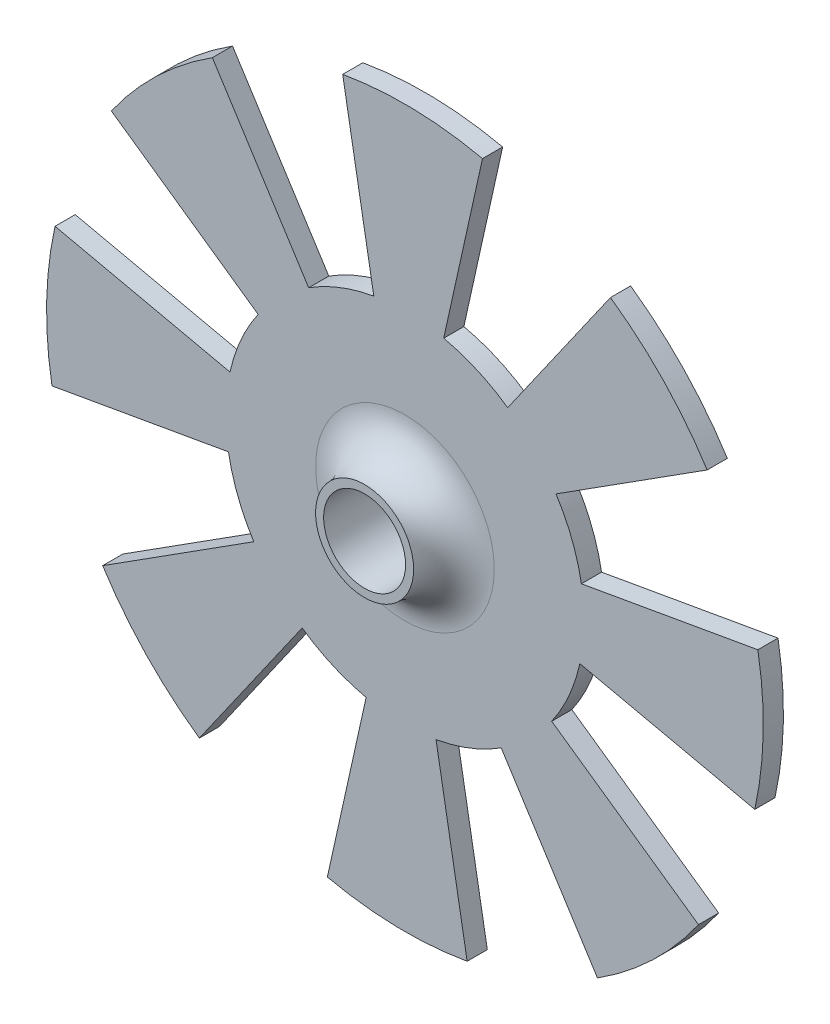
SolidWorks part; units mm, degrees
ref_plane "Front Plane" through (0, 0, 0) normal (0, 0, 1) x (1, 0, 0)
ref_plane "Top Plane" through (0, 0, 0) normal (0, 1, 0) x (1, 0, 0)
ref_plane "Right Plane" through (0, 0, 0) normal (1, 0, 0) x (0, 0, -1)
sketch "Sketch1" plane through (0, 0, 0) normal (0, 0, 1) x (1, 0, 0)
  circle A0 centre (0, 0) radius 8.89
  circle A1 centre (0, 0) radius 1.016
  dimension "D1" = 17.78
  dimension "D2" = 2.032
extrude "Boss-Extrude1" add sketch "Sketch1" against normal blind 0.5
sketch "Sketch2" plane through (0, 0, 0) normal (0, 0, 1) x (1, 0, 0)
  line L0 (-0.7719, 4.3775) -> (-1.5437, 8.7549)
  line L1 (2.5495, 3.6411) -> (5.0991, 7.2823)
  line L2 (4.3775, 0.7719) -> (8.7549, 1.5437)
  line L3 (3.6411, -2.5495) -> (7.2823, -5.0991)
  line L4 (0.7719, -4.3775) -> (1.5437, -8.7549)
  line L5 (-2.5495, -3.6411) -> (-5.0991, -7.2823)
  line L6 (-4.3775, -0.7719) -> (-8.7549, -1.5437)
  line L7 (-3.6411, 2.5495) -> (-7.2823, 5.0991)
  line L8 (0.9621, 4.3396) -> (1.9241, 8.6793)
  line L9 (2.5495, 3.6411) -> (5.0991, 7.2823)
  line L10 (3.7489, 2.3883) -> (7.4977, 4.7766)
  line L11 (4.3775, 0.7719) -> (8.7549, 1.5437)
  line L12 (4.3396, -0.9621) -> (8.6793, -1.9241)
  line L13 (3.6411, -2.5495) -> (7.2823, -5.0991)
  line L14 (2.3883, -3.7489) -> (4.7766, -7.4977)
  line L15 (0.7719, -4.3775) -> (1.5437, -8.7549)
  line L16 (-0.9621, -4.3396) -> (-1.9241, -8.6793)
  line L17 (-2.5495, -3.6411) -> (-5.0991, -7.2823)
  line L18 (-3.7489, -2.3883) -> (-7.4977, -4.7766)
  line L19 (-4.3775, -0.7719) -> (-8.7549, -1.5437)
  line L20 (-4.3396, 0.9621) -> (-8.6793, 1.9241)
  line L21 (-3.6411, 2.5495) -> (-7.2823, 5.0991)
  line L22 (-2.3883, 3.7489) -> (-4.7766, 7.4977)
  arc A0 (-0.7719, 4.3775) -> (-2.3883, 3.7489) centre (0, 0) ccw
  circle A1 centre (0, 0) radius 8.89 construction
  arc A2 (-3.6411, 2.5495) -> (-4.3396, 0.9621) centre (0, 0) ccw
  circle A3 centre (0, 0) radius 8.89
  arc A4 (8.7549, 1.5437) -> (1.9241, 8.6793) centre (0, 0) ccw
  arc A5 (2.5495, 3.6411) -> (0.9621, 4.3396) centre (0, 0) ccw
  arc A6 (4.3775, 0.7719) -> (3.7489, 2.3883) centre (0, 0) ccw
  arc A7 (3.6411, -2.5495) -> (4.3396, -0.9621) centre (0, 0) ccw
  arc A8 (7.2823, -5.0991) -> (8.6793, -1.9241) centre (0, 0) ccw
  arc A9 (1.5437, -8.7549) -> (4.7766, -7.4977) centre (0, 0) ccw
  arc A10 (0.7719, -4.3775) -> (2.3883, -3.7489) centre (0, 0) ccw
  arc A11 (-2.5495, -3.6411) -> (-0.9621, -4.3396) centre (0, 0) ccw
  arc A12 (-5.0991, -7.2823) -> (-1.9241, -8.6793) centre (0, 0) ccw
  arc A13 (-8.7549, -1.5437) -> (-7.4977, -4.7766) centre (0, 0) ccw
  arc A14 (-4.3775, -0.7719) -> (-3.7489, -2.3883) centre (0, 0) ccw
  arc A15 (-1.5437, 8.7549) -> (-4.7766, 7.4977) centre (0, 0) ccw
  arc A16 (-7.2823, 5.0991) -> (-8.6793, 1.9241) centre (0, 0) ccw
  point P18 (0, 0)
  point P34 (0, 0)
  circle M13 centre (0, 0) radius 8.89
  dimension "D1" = 8.89
  dimension "D3" = 45
  dimension "D2" = 0
  dimension "D4" = 4
extrude "Cut-Extrude1" cut sketch "Sketch2" against normal blind 0.5 contours A0 L0 L22 M13 | A5 L1 L8 M13 | A6 L2 L10 M13 | A7 L3 L12 M13 | A10 L4 L14 M13 | A11 L5 L16 M13 | A14 L6 L18 M13 | A2 L7 L20 M13 region at (-2.49, 6.403, 0) region at (2.7669, 6.2883, 0) region at (-6.2883, 2.7669, 0) region at (6.403, 2.49, 0) region at (-6.403, -2.49, 0) region at (6.2883, -2.7669, 0) region at (-2.7669, -6.2883, 0) region at (2.49, -6.403, 0)
sketch "Sketch3" plane through (0, 0, 0) normal (0, 0, 1) x (1, 0, 0)
  circle A0 centre (0, 0) radius 1.016 construction
  circle A1 centre (0, 0) radius 1.016
  circle A2 centre (0, 0) radius 1.216
  dimension "D1" = 0.2
extrude "Boss-Extrude2" add sketch "Sketch3" along normal blind 1
fillet "Fillet1" radius 1 1 edges at (1.216, 0, 0)
